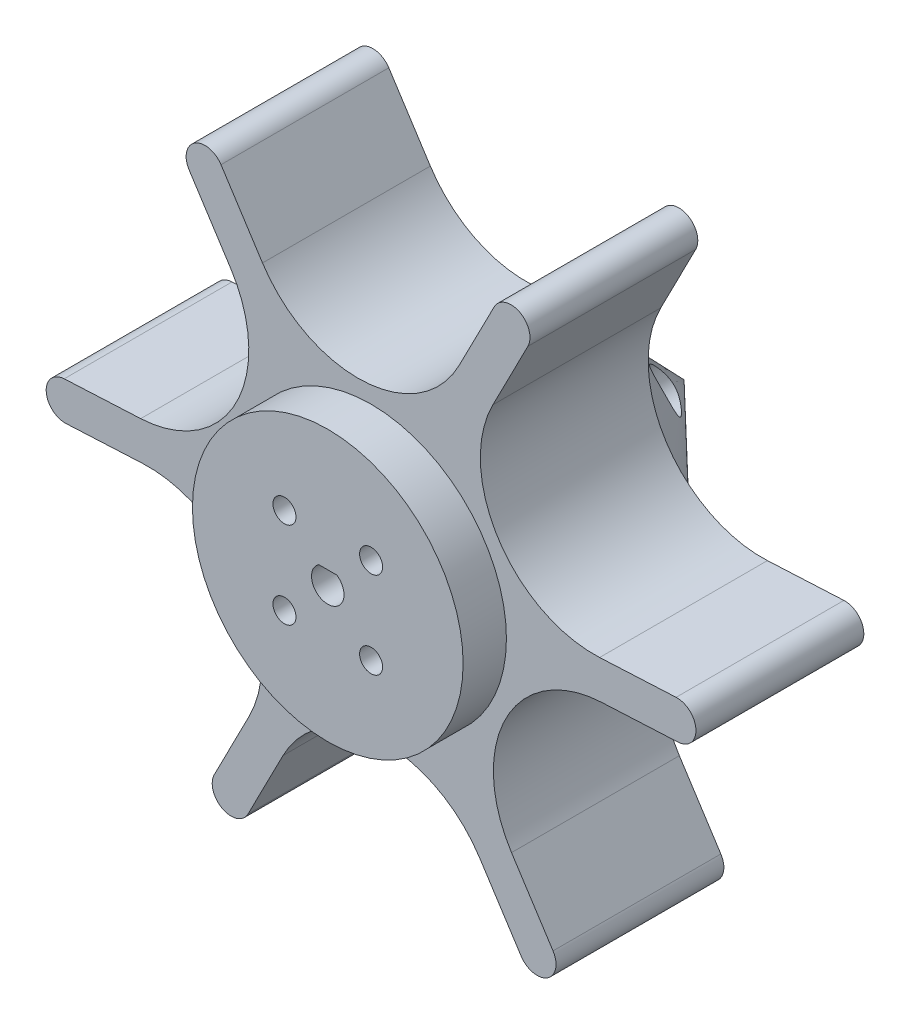
SolidWorks part; units mm, degrees
ref_plane "Front Plane" through (0, 0, 0) normal (0, 0, 1) x (1, 0, 0)
ref_plane "Top Plane" through (0, 0, 0) normal (0, 1, 0) x (1, 0, 0)
ref_plane "Right Plane" through (0, 0, 0) normal (1, 0, 0) x (0, 0, -1)
sketch "Sketch1" plane through (0, 0, 0) normal (0, 0, 1) x (1, 0, 0)
  line L0 (-33.6058, 45.6534) -> (-25.9397, 33.7658)
  line L1 (-30.6644, 47.5503) -> (-56.5119, -2.781) construction
  line L2 (-56.5119, -2.781) -> (-25.8475, -50.3313) construction
  line L3 (-25.8475, -50.3313) -> (30.6644, -47.5503) construction
  line L4 (30.6644, -47.5503) -> (56.5119, 2.781) construction
  line L5 (56.5119, 2.781) -> (25.8475, 50.3313) construction
  line L6 (25.8475, 50.3313) -> (-30.6644, 47.5503) construction
  line L7 (-27.723, 49.4471) -> (-20.0569, 37.5596)
  line L8 (22.7341, 51.9302) -> (16.2722, 39.3474)
  line L9 (28.961, 48.7324) -> (22.4991, 36.1496)
  line L10 (56.3399, 6.2768) -> (42.2119, 5.5815)
  line L11 (56.684, -0.7147) -> (42.556, -1.41)
  line L12 (33.6058, -45.6534) -> (25.9397, -33.7658)
  line L13 (27.723, -49.4471) -> (20.0569, -37.5596)
  line L14 (-22.7341, -51.9302) -> (-16.2722, -39.3474)
  line L15 (-28.961, -48.7324) -> (-22.4991, -36.1496)
  line L16 (-56.3399, -6.2768) -> (-42.2119, -5.5815)
  line L17 (-56.684, 0.7147) -> (-42.556, 1.41)
  circle A0 centre (41.1797, 26.5562) radius 21 construction
  circle A1 centre (43.5882, -22.3846) radius 21 construction
  circle A2 centre (2.4085, -48.9408) radius 21 construction
  circle A3 centre (-41.1797, -26.5562) radius 21 construction
  circle A4 centre (-43.5882, 22.3846) radius 21 construction
  circle A5 centre (-2.4085, 48.9408) radius 21 construction
  circle A6 centre (0, 0) radius 49 construction
  circle A7 centre (-30.6644, 47.5503) radius 3.5
  circle A8 centre (25.8475, 50.3313) radius 3.5
  circle A9 centre (56.5119, 2.781) radius 3.5
  circle A10 centre (30.6644, -47.5503) radius 3.5
  circle A11 centre (-25.8475, -50.3313) radius 3.5
  circle A12 centre (-56.5119, -2.781) radius 3.5
  arc A13 (-42.556, 1.41) -> (-25.9397, 33.7658) centre (-43.5882, 22.3846) ccw
  arc A14 (-20.0569, 37.5596) -> (16.2722, 39.3474) centre (-2.4085, 48.9408) ccw
  arc A15 (22.4991, 36.1496) -> (42.2119, 5.5815) centre (41.1797, 26.5562) ccw
  arc A16 (42.556, -1.41) -> (25.9397, -33.7658) centre (43.5882, -22.3846) ccw
  arc A17 (20.0569, -37.5596) -> (-16.2722, -39.3474) centre (2.4085, -48.9408) ccw
  arc A18 (-22.4991, -36.1496) -> (-42.2119, -5.5815) centre (-41.1797, -26.5562) ccw
  point P25 (0, 0)
  point P36 (0, 0)
  point P60 (0, 0)
  point P77 (0, 0)
  dimension "D2" = 42
  dimension "D4" = 7
  dimension "D1" = 6
  dimension "D3" = 6
  dimension "D5" = 6
  dimension "D6" = 6
extrude "Boss-Extrude1" add sketch "Sketch1" along normal blind 21 contours A18 L15 A11 L14 A17 L13 A10 L12 A16 L11 A9 L10 A15 L9 A8 L8 A14 L7 A7 L0 A13 L17 A12 L16 | A12 | A7 | A8 | A9 | A10 | A11 region at (0, 0, 0) region at (-30.6644, 47.5503, 0) region at (-56.5119, -2.781, 0) region at (25.8475, 50.3313, 0) region at (-25.8475, -50.3313, 0) region at (56.5119, 2.781, 0) region at (30.6644, -47.5503, 0)
ref_plane "Plane1" through (0, 0, 0) normal (0.0492, -0.9988, 0) x (-0.9988, -0.0492, 0)
sketch "Sketch3" plane through (0, 0, 0) normal (0.0492, -0.9988, 0) x (-0.9988, -0.0492, 0)
  line L0 (0, 0) -> (-28, 0)
  line L1 (-28, 0) -> (0, 26.8135)
  line L2 (0, 26.8135) -> (0, 0)
  dimension "D1" = 28
revolve "Revolve1" add sketch "Sketch3" angle 360 about L2
sketch "Sketch4" plane through (0, 0, 21) normal (0, 0, 1) x (1, 0, 0)
  circle A0 centre (0, 0) radius 25
  dimension "D1" = 50
extrude "Boss-Extrude2" add sketch "Sketch4" along normal blind 18
sketch "Sketch5" plane through (0, 0, 39) normal (0, 0, 1) x (1, 0, 0)
  line L0 (-1.6583, 2.5) -> (1.6583, 2.5)
  arc A0 (-1.6583, 2.5) -> (1.6583, 2.5) centre (0, 0) ccw
  dimension "D1" = 6
  dimension "D2" = 2.5
extrude "Cut-Extrude2" cut sketch "Sketch5" against normal blind 20 contours A0 region at (0, -0.112, 39)
ref_plane "Plane2" through (-1.2288, 24.9698, 0) normal (-0.0492, 0.9988, 0) x (0.9988, 0.0492, 0)
ref_plane "Plane5" through (1.2288, -24.9698, 0) normal (0.0492, -0.9988, 0) x (-0.9988, -0.0492, 0)
sketch "Sketch7" plane through (0, 0, 39) normal (0, 0, 1) x (1, 0, 0)
  line L0 (0, 12.9158) -> (0, -15.3556) construction
  line L1 (-12.6694, 0) -> (16.084, 0) construction
  circle A0 centre (-8, 8) radius 2.125
  circle A1 centre (8, 8) radius 2.125
  circle A2 centre (8, -8) radius 2.125
  circle A3 centre (-8, -8) radius 2.125
  dimension "D1" = 4.25
  dimension "D2" = 8
  dimension "D3" = 8
extrude "Cut-Extrude3" cut sketch "Sketch7" against normal through all
sketch "Sketch9" plane through (0, 0, 0) normal (0, 0, -1) x (-1, 0, 0)
  line L0 (0, 0) -> (24.2952, 0) construction
  line L1 (0, 0) -> (0, 21.4598) construction
  circle A1 centre (-8, 8) radius 2.125 construction
  circle A5 centre (-8, 8) radius 2.125 construction
  circle A8 centre (-8, 8) radius 4
  circle A10 centre (8, 8) radius 4
  circle A11 centre (8, -8) radius 4
  circle A12 centre (-8, -8) radius 4
  dimension "D1" = 8
extrude "Cut-Extrude4" cut sketch "Sketch9" against normal offset from surface 3 and the other way through all up to face at (-10.125, -8, 39)
sketch "Sketch10" plane through (0, 0, 21) normal (0, 0, 1) x (1, 0, 0)
  line L12 (-22.4991, -36.1496) -> (-28.961, -48.7324)
  line L13 (-22.7341, -51.9302) -> (-16.2722, -39.3474)
  line L14 (20.0569, -37.5596) -> (27.723, -49.4471)
  line L15 (33.6058, -45.6534) -> (25.9397, -33.7658)
  line L16 (42.556, -1.41) -> (56.684, -0.7147)
  line L17 (56.3399, 6.2768) -> (42.2119, 5.5815)
  line L18 (22.4991, 36.1496) -> (28.961, 48.7324)
  line L19 (22.7341, 51.9302) -> (16.2722, 39.3474)
  line L20 (-20.0569, 37.5596) -> (-27.723, 49.4471)
  line L21 (-33.6058, 45.6534) -> (-25.9397, 33.7658)
  line L22 (-42.556, 1.41) -> (-56.684, 0.7147)
  line L23 (-56.3399, -6.2768) -> (-42.2119, -5.5815)
  line L24 (-22.4991, -36.1496) -> (-28.961, -48.7324)
  line L25 (-22.7341, -51.9302) -> (-16.2722, -39.3474)
  line L26 (20.0569, -37.5596) -> (27.723, -49.4471)
  line L27 (33.6058, -45.6534) -> (25.9397, -33.7658)
  line L28 (42.556, -1.41) -> (56.684, -0.7147)
  line L29 (56.3399, 6.2768) -> (42.2119, 5.5815)
  line L30 (22.4991, 36.1496) -> (28.961, 48.7324)
  line L31 (22.7341, 51.9302) -> (16.2722, 39.3474)
  line L32 (-20.0569, 37.5596) -> (-27.723, 49.4471)
  line L33 (-33.6058, 45.6534) -> (-25.9397, 33.7658)
  line L34 (-42.556, 1.41) -> (-56.684, 0.7147)
  line L35 (-56.3399, -6.2768) -> (-42.2119, -5.5815)
  arc A12 (-22.4991, -36.1496) -> (-42.2119, -5.5815) centre (-41.1797, -26.5562) ccw
  arc A13 (-28.961, -48.7324) -> (-22.7341, -51.9302) centre (-25.8475, -50.3313) ccw
  arc A14 (20.0569, -37.5596) -> (-16.2722, -39.3474) centre (2.4085, -48.9408) ccw
  arc A15 (27.723, -49.4471) -> (33.6058, -45.6534) centre (30.6644, -47.5503) ccw
  arc A16 (42.556, -1.41) -> (25.9397, -33.7658) centre (43.5882, -22.3846) ccw
  arc A17 (56.684, -0.7147) -> (56.3399, 6.2768) centre (56.5119, 2.781) ccw
  arc A18 (22.4991, 36.1496) -> (42.2119, 5.5815) centre (41.1797, 26.5562) ccw
  arc A19 (28.961, 48.7324) -> (22.7341, 51.9302) centre (25.8475, 50.3313) ccw
  arc A20 (-20.0569, 37.5596) -> (16.2722, 39.3474) centre (-2.4085, 48.9408) ccw
  arc A21 (-27.723, 49.4471) -> (-33.6058, 45.6534) centre (-30.6644, 47.5503) ccw
  arc A22 (-42.556, 1.41) -> (-25.9397, 33.7658) centre (-43.5882, 22.3846) ccw
  arc A23 (-56.684, 0.7147) -> (-56.3399, -6.2768) centre (-56.5119, -2.781) ccw
  arc A24 (-22.4991, -36.1496) -> (-42.2119, -5.5815) centre (-41.1797, -26.5562) ccw
  arc A25 (-28.961, -48.7324) -> (-22.7341, -51.9302) centre (-25.8475, -50.3313) ccw
  arc A26 (20.0569, -37.5596) -> (-16.2722, -39.3474) centre (2.4085, -48.9408) ccw
  arc A27 (27.723, -49.4471) -> (33.6058, -45.6534) centre (30.6644, -47.5503) ccw
  arc A28 (42.556, -1.41) -> (25.9397, -33.7658) centre (43.5882, -22.3846) ccw
  arc A29 (56.684, -0.7147) -> (56.3399, 6.2768) centre (56.5119, 2.781) ccw
  arc A30 (22.4991, 36.1496) -> (42.2119, 5.5815) centre (41.1797, 26.5562) ccw
  arc A31 (28.961, 48.7324) -> (22.7341, 51.9302) centre (25.8475, 50.3313) ccw
  arc A32 (-20.0569, 37.5596) -> (16.2722, 39.3474) centre (-2.4085, 48.9408) ccw
  arc A33 (-27.723, 49.4471) -> (-33.6058, 45.6534) centre (-30.6644, 47.5503) ccw
  arc A34 (-42.556, 1.41) -> (-25.9397, 33.7658) centre (-43.5882, 22.3846) ccw
  arc A35 (-56.684, 0.7147) -> (-56.3399, -6.2768) centre (-56.5119, -2.781) ccw
  dimension "D1" = 0
extrude "Boss-Extrude3" add sketch "Sketch10" along normal blind 10
